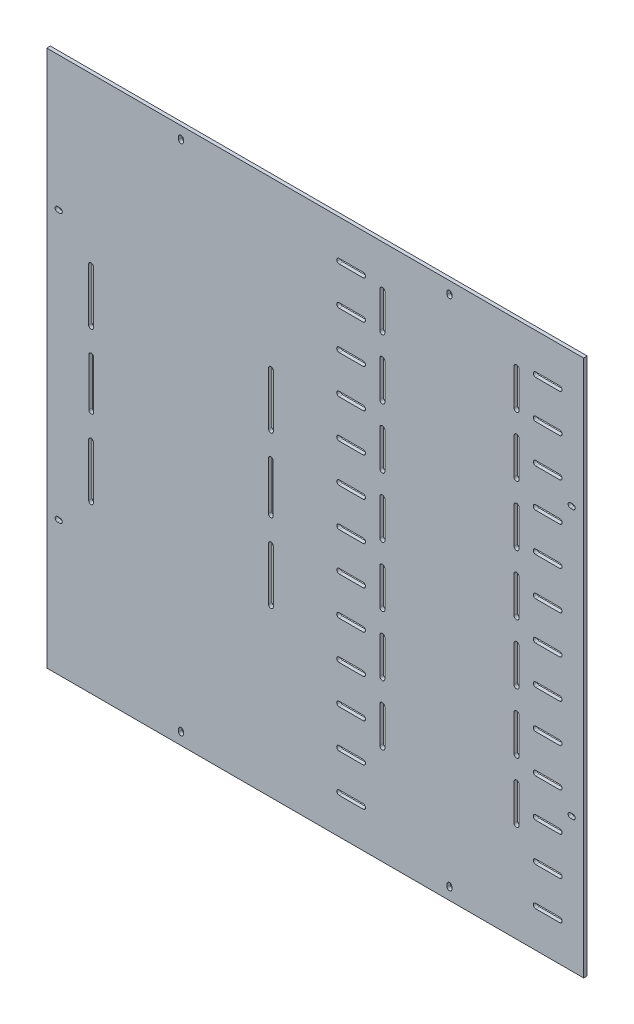
SolidWorks part; units mm, degrees
ref_plane "Piano frontale" through (0, 0, 0) normal (0, 0, 1) x (1, 0, 0)
ref_plane "Piano superiore" through (0, 0, 0) normal (0, 1, 0) x (1, 0, 0)
ref_plane "Piano destro" through (0, 0, 0) normal (1, 0, 0) x (0, 0, -1)
sketch "Schizzo1" plane through (0, 0, 0) normal (0, 0, 1) x (1, 0, 0)
  line L0 (10, 448) -> (10, -28.2593) construction
  line L1 (0, 0) -> (448, 0)
  line L2 (0, 0) -> (0, 448)
  line L3 (0, 448) -> (448, 448)
  line L4 (448, 0) -> (448, 448)
  line L5 (0, 224) -> (448, 224) construction
  line L6 (224, 448) -> (224, 0) construction
  line L7 (438, 448) -> (438, -28.2593) construction
  line L8 (0, 438) -> (525.0128, 438) construction
  line L9 (0, 10) -> (525.0128, 10) construction
  line L10 (0, 448) -> (0, 224) construction
  line L11 (0, 448) -> (0, 224) construction
  line L12 (9, 336) -> (11, 336) construction
  line L13 (9, 338) -> (11, 338)
  line L14 (9, 334) -> (11, 334)
  line L15 (0, 336) -> (224, 336) construction
  line L16 (9, 112) -> (11, 112) construction
  line L17 (9, 110) -> (11, 110)
  line L18 (9, 114) -> (11, 114)
  line L19 (439, 112) -> (437, 112) construction
  line L20 (439, 110) -> (437, 110)
  line L21 (439, 114) -> (437, 114)
  line L22 (439, 336) -> (437, 336) construction
  line L23 (439, 338) -> (437, 338)
  line L24 (439, 334) -> (437, 334)
  line L25 (112, 448) -> (112, 224) construction
  line L26 (112, 439) -> (112, 437) construction
  line L27 (114, 439) -> (114, 437)
  line L28 (110, 439) -> (110, 437)
  line L29 (336, 439) -> (336, 437) construction
  line L30 (334, 439) -> (334, 437)
  line L31 (338, 439) -> (338, 437)
  line L32 (112, 9) -> (112, 11) construction
  line L33 (114, 9) -> (114, 11)
  line L34 (110, 9) -> (110, 11)
  line L35 (336, 9) -> (336, 11) construction
  line L36 (334, 9) -> (334, 11)
  line L37 (338, 9) -> (338, 11)
  line L38 (36.9588, 287.1268) -> (36.9588, 448) construction
  line L39 (36.9588, 265.3661) -> (36.9588, 309.3661) construction
  line L40 (34.9588, 265.3661) -> (34.9588, 309.3661)
  line L41 (38.9588, 265.3661) -> (38.9588, 309.3661)
  line L42 (36.9588, 182.6339) -> (36.9588, 138.6339) construction
  line L43 (34.9588, 182.6339) -> (34.9588, 138.6339)
  line L44 (38.9588, 182.6339) -> (38.9588, 138.6339)
  line L45 (37.087, 204.1388) -> (37.087, 244.1388) construction
  line L46 (35.087, 204.1388) -> (35.087, 244.1388)
  line L47 (39.087, 204.1388) -> (39.087, 244.1388)
  line L48 (187.0412, 265.3661) -> (187.0412, 309.3661) construction
  line L49 (189.0412, 265.3661) -> (189.0412, 309.3661)
  line L50 (185.0412, 265.3661) -> (185.0412, 309.3661)
  line L51 (186.913, 204.1388) -> (186.913, 244.1388) construction
  line L52 (188.913, 204.1388) -> (188.913, 244.1388)
  line L53 (184.913, 204.1388) -> (184.913, 244.1388)
  line L54 (187.0412, 182.6339) -> (187.0412, 138.6339) construction
  line L55 (189.0412, 182.6339) -> (189.0412, 138.6339)
  line L56 (185.0412, 182.6339) -> (185.0412, 138.6339)
  line L57 (243.9707, 416) -> (263.9707, 416) construction
  line L58 (243.9707, 418) -> (263.9707, 418)
  line L59 (243.9707, 414) -> (263.9707, 414)
  line L63 (224, 224) -> (448, 0) construction
  line L64 (448, 224) -> (224, 0) construction
  line L65 (224, 224) -> (448, 224) construction
  line L66 (336, 112) -> (335.9892, 224.0001) construction
  line L67 (336, 112) -> (448, 112) construction
  line L83 (427.9707, 416.0177) -> (407.9707, 416.0139) construction
  line L84 (427.9703, 418.0177) -> (407.9703, 418.0139)
  line L85 (427.9711, 414.0177) -> (407.9711, 414.0139)
  line L89 (243.9707, 384) -> (263.9707, 384) construction
  line L90 (243.9707, 386) -> (263.9707, 386)
  line L91 (243.9707, 382) -> (263.9707, 382)
  line L92 (427.9707, 384.0177) -> (407.9707, 384.0139) construction
  line L93 (427.9703, 386.0177) -> (407.9703, 386.0139)
  line L94 (427.9711, 382.0177) -> (407.9711, 382.0139)
  line L95 (279.9725, 383.005) -> (279.9725, 412.995) construction
  line L96 (277.8725, 383.005) -> (277.8725, 412.995)
  line L97 (282.0725, 383.005) -> (282.0725, 412.995)
  line L98 (243.9707, 352) -> (263.9707, 352) construction
  line L99 (243.9707, 354) -> (263.9707, 354)
  line L100 (243.9707, 350) -> (263.9707, 350)
  line L101 (427.9707, 352.0177) -> (407.9707, 352.0139) construction
  line L102 (427.9703, 354.0177) -> (407.9703, 354.0139)
  line L103 (427.9711, 350.0177) -> (407.9711, 350.0139)
  line L104 (243.9707, 320) -> (263.9707, 320) construction
  line L105 (243.9707, 322) -> (263.9707, 322)
  line L106 (243.9707, 318) -> (263.9707, 318)
  line L107 (427.9707, 320.0177) -> (407.9707, 320.0139) construction
  line L108 (427.9703, 322.0177) -> (407.9703, 322.0139)
  line L109 (427.9711, 318.0177) -> (407.9711, 318.0139)
  line L110 (243.9707, 288) -> (263.9707, 288) construction
  line L111 (391.9724, 383.0058) -> (391.9724, 413.0158) construction
  line L112 (394.0724, 383.0058) -> (394.0724, 413.0158)
  line L113 (389.8724, 383.0058) -> (389.8724, 413.0158)
  line L114 (336, 112) -> (202.345, 112) construction
  line L118 (243.9707, 290) -> (263.9707, 290)
  line L122 (243.9707, 286) -> (263.9707, 286)
  line L132 (427.9707, 288.0177) -> (407.9707, 288.0139) construction
  line L133 (427.9703, 290.0177) -> (407.9703, 290.0139)
  line L134 (427.9711, 286.0177) -> (407.9711, 286.0139)
  line L135 (243.9707, 256) -> (263.9707, 256) construction
  line L136 (243.9707, 258) -> (263.9707, 258)
  line L137 (243.9707, 254) -> (263.9707, 254)
  line L138 (427.9707, 256.0177) -> (407.9707, 256.0139) construction
  line L139 (427.9703, 258.0177) -> (407.9703, 258.0139)
  line L140 (427.9711, 254.0177) -> (407.9711, 254.0139)
  line L141 (243.9707, 224) -> (263.9707, 224) construction
  line L142 (243.9707, 226) -> (263.9707, 226)
  line L143 (243.9707, 222) -> (263.9707, 222)
  line L144 (427.9707, 224.0177) -> (407.9707, 224.0139) construction
  line L145 (427.9703, 226.0177) -> (407.9703, 226.0139)
  line L146 (427.9711, 222.0177) -> (407.9711, 222.0139)
  line L147 (243.9707, 192) -> (263.9707, 192) construction
  line L148 (243.9707, 194) -> (263.9707, 194)
  line L149 (243.9707, 190) -> (263.9707, 190)
  line L150 (427.9707, 192.0177) -> (407.9707, 192.0139) construction
  line L151 (427.9703, 194.0177) -> (407.9703, 194.0139)
  line L152 (427.9711, 190.0177) -> (407.9711, 190.0139)
  line L153 (243.9707, 160) -> (263.9707, 160) construction
  line L154 (243.9707, 162) -> (263.9707, 162)
  line L155 (243.9707, 158) -> (263.9707, 158)
  line L156 (427.9707, 160.0177) -> (407.9707, 160.0139) construction
  line L157 (427.9703, 162.0177) -> (407.9703, 162.0139)
  line L158 (427.9711, 158.0177) -> (407.9711, 158.0139)
  line L159 (243.9707, 128) -> (263.9707, 128) construction
  line L160 (243.9707, 130) -> (263.9707, 130)
  line L161 (243.9707, 126) -> (263.9707, 126)
  line L162 (427.9707, 128.0177) -> (407.9707, 128.0139) construction
  line L163 (427.9703, 130.0177) -> (407.9703, 130.0139)
  line L164 (427.9711, 126.0177) -> (407.9711, 126.0139)
  line L165 (279.9725, 333.005) -> (279.9725, 362.995) construction
  line L166 (277.8725, 333.005) -> (277.8725, 362.995)
  line L167 (282.0725, 333.005) -> (282.0725, 362.995)
  line L168 (391.9724, 333.0058) -> (391.9724, 363.0158) construction
  line L169 (394.0724, 333.0058) -> (394.0724, 363.0158)
  line L170 (389.8724, 333.0058) -> (389.8724, 363.0158)
  line L171 (279.9725, 283.005) -> (279.9725, 312.995) construction
  line L172 (277.8725, 283.005) -> (277.8725, 312.995)
  line L173 (282.0725, 283.005) -> (282.0725, 312.995)
  line L174 (391.9724, 283.0058) -> (391.9724, 313.0158) construction
  line L175 (394.0724, 283.0058) -> (394.0724, 313.0158)
  line L176 (389.8724, 283.0058) -> (389.8724, 313.0158)
  line L177 (279.9725, 233.005) -> (279.9725, 262.995) construction
  line L178 (277.8725, 233.005) -> (277.8725, 262.995)
  line L179 (282.0725, 233.005) -> (282.0725, 262.995)
  line L180 (391.9724, 233.0058) -> (391.9724, 263.0158) construction
  line L181 (394.0724, 233.0058) -> (394.0724, 263.0158)
  line L182 (389.8724, 233.0058) -> (389.8724, 263.0158)
  line L183 (279.9725, 183.005) -> (279.9725, 212.995) construction
  line L184 (277.8725, 183.005) -> (277.8725, 212.995)
  line L185 (282.0725, 183.005) -> (282.0725, 212.995)
  line L186 (391.9724, 183.0058) -> (391.9724, 213.0158) construction
  line L187 (394.0724, 183.0058) -> (394.0724, 213.0158)
  line L188 (389.8724, 183.0058) -> (389.8724, 213.0158)
  line L189 (279.9725, 133.005) -> (279.9725, 162.995) construction
  line L190 (277.8725, 133.005) -> (277.8725, 162.995)
  line L191 (282.0725, 133.005) -> (282.0725, 162.995)
  line L192 (391.9724, 133.0058) -> (391.9724, 163.0158) construction
  line L193 (394.0724, 133.0058) -> (394.0724, 163.0158)
  line L194 (389.8724, 133.0058) -> (389.8724, 163.0158)
  line L195 (279.9725, 83.005) -> (279.9725, 112.995) construction
  line L196 (277.8725, 83.005) -> (277.8725, 112.995)
  line L197 (282.0725, 83.005) -> (282.0725, 112.995)
  line L198 (391.9724, 83.0058) -> (391.9724, 113.0158) construction
  line L199 (394.0724, 83.0058) -> (394.0724, 113.0158)
  line L200 (389.8724, 83.0058) -> (389.8724, 113.0158)
  line L201 (243.9707, 96) -> (263.9707, 96) construction
  line L202 (243.9707, 98) -> (263.9707, 98)
  line L203 (243.9707, 94) -> (263.9707, 94)
  line L204 (427.9707, 96.0177) -> (407.9707, 96.0139) construction
  line L205 (427.9703, 98.0177) -> (407.9703, 98.0139)
  line L206 (427.9711, 94.0177) -> (407.9711, 94.0139)
  line L207 (243.9707, 64) -> (263.9707, 64) construction
  line L208 (243.9707, 66) -> (263.9707, 66)
  line L209 (243.9707, 62) -> (263.9707, 62)
  line L210 (427.9707, 64.0177) -> (407.9707, 64.0139) construction
  line L211 (427.9703, 66.0177) -> (407.9703, 66.0139)
  line L212 (427.9711, 62.0177) -> (407.9711, 62.0139)
  line L213 (243.9707, 32) -> (263.9707, 32) construction
  line L214 (243.9707, 34) -> (263.9707, 34)
  line L215 (243.9707, 30) -> (263.9707, 30)
  line L216 (427.9707, 32.0177) -> (407.9707, 32.0139) construction
  line L217 (427.9703, 34.0177) -> (407.9703, 34.0139)
  line L218 (427.9711, 30.0177) -> (407.9711, 30.0139)
  arc A0 (9, 338) -> (9, 334) centre (9, 336) ccw
  arc A1 (11, 334) -> (11, 338) centre (11, 336) ccw
  arc A2 (9, 110) -> (9, 114) centre (9, 112) cw
  arc A3 (11, 114) -> (11, 110) centre (11, 112) cw
  arc A4 (439, 110) -> (439, 114) centre (439, 112) ccw
  arc A5 (437, 114) -> (437, 110) centre (437, 112) ccw
  arc A6 (439, 338) -> (439, 334) centre (439, 336) cw
  arc A7 (437, 334) -> (437, 338) centre (437, 336) cw
  arc A8 (114, 439) -> (110, 439) centre (112, 439) ccw
  arc A9 (110, 437) -> (114, 437) centre (112, 437) ccw
  arc A10 (334, 439) -> (338, 439) centre (336, 439) cw
  arc A11 (338, 437) -> (334, 437) centre (336, 437) cw
  arc A12 (114, 9) -> (110, 9) centre (112, 9) cw
  arc A13 (110, 11) -> (114, 11) centre (112, 11) cw
  arc A14 (334, 9) -> (338, 9) centre (336, 9) ccw
  arc A15 (338, 11) -> (334, 11) centre (336, 11) ccw
  arc A16 (34.9588, 265.3661) -> (38.9588, 265.3661) centre (36.9588, 265.3661) ccw
  arc A17 (38.9588, 309.3661) -> (34.9588, 309.3661) centre (36.9588, 309.3661) ccw
  arc A18 (34.9588, 182.6339) -> (38.9588, 182.6339) centre (36.9588, 182.6339) cw
  arc A19 (38.9588, 138.6339) -> (34.9588, 138.6339) centre (36.9588, 138.6339) cw
  arc A20 (35.087, 204.1388) -> (39.087, 204.1388) centre (37.087, 204.1388) ccw
  arc A21 (39.087, 244.1388) -> (35.087, 244.1388) centre (37.087, 244.1388) ccw
  arc A22 (189.0412, 265.3661) -> (185.0412, 265.3661) centre (187.0412, 265.3661) cw
  arc A23 (185.0412, 309.3661) -> (189.0412, 309.3661) centre (187.0412, 309.3661) cw
  arc A24 (188.913, 204.1388) -> (184.913, 204.1388) centre (186.913, 204.1388) cw
  arc A25 (184.913, 244.1388) -> (188.913, 244.1388) centre (186.913, 244.1388) cw
  arc A26 (189.0412, 182.6339) -> (185.0412, 182.6339) centre (187.0412, 182.6339) ccw
  arc A27 (185.0412, 138.6339) -> (189.0412, 138.6339) centre (187.0412, 138.6339) ccw
  arc A28 (243.9707, 418) -> (243.9707, 414) centre (243.9707, 416) ccw
  arc A29 (263.9707, 414) -> (263.9707, 418) centre (263.9707, 416) ccw
  arc A36 (427.9703, 418.0177) -> (427.9711, 414.0177) centre (427.9707, 416.0177) cw
  arc A37 (407.9711, 414.0139) -> (407.9703, 418.0139) centre (407.9707, 416.0139) cw
  arc A38 (243.9707, 386) -> (243.9707, 382) centre (243.9707, 384) ccw
  arc A39 (263.9707, 382) -> (263.9707, 386) centre (263.9707, 384) ccw
  arc A40 (427.9703, 386.0177) -> (427.9711, 382.0177) centre (427.9707, 384.0177) cw
  arc A41 (407.9711, 382.0139) -> (407.9703, 386.0139) centre (407.9707, 384.0139) cw
  arc A42 (243.9707, 354) -> (243.9707, 350) centre (243.9707, 352) ccw
  arc A43 (263.9707, 350) -> (263.9707, 354) centre (263.9707, 352) ccw
  arc A44 (427.9703, 354.0177) -> (427.9711, 350.0177) centre (427.9707, 352.0177) cw
  arc A45 (407.9711, 350.0139) -> (407.9703, 354.0139) centre (407.9707, 352.0139) cw
  arc A52 (243.9707, 322) -> (243.9707, 318) centre (243.9707, 320) ccw
  arc A53 (263.9707, 318) -> (263.9707, 322) centre (263.9707, 320) ccw
  arc A56 (427.9703, 322.0177) -> (427.9711, 318.0177) centre (427.9707, 320.0177) cw
  arc A57 (407.9711, 318.0139) -> (407.9703, 322.0139) centre (407.9707, 320.0139) cw
  arc A58 (243.9707, 290) -> (243.9707, 286) centre (243.9707, 288) ccw
  arc A59 (263.9707, 286) -> (263.9707, 290) centre (263.9707, 288) ccw
  arc A60 (277.8725, 383.005) -> (282.0725, 383.005) centre (279.9725, 383.005) ccw
  arc A61 (282.0725, 412.995) -> (277.8725, 412.995) centre (279.9725, 412.995) ccw
  arc A62 (427.9703, 290.0177) -> (427.9711, 286.0177) centre (427.9707, 288.0177) cw
  arc A63 (407.9711, 286.0139) -> (407.9703, 290.0139) centre (407.9707, 288.0139) cw
  arc A64 (243.9707, 258) -> (243.9707, 254) centre (243.9707, 256) ccw
  arc A65 (263.9707, 254) -> (263.9707, 258) centre (263.9707, 256) ccw
  arc A66 (427.9703, 258.0177) -> (427.9711, 254.0177) centre (427.9707, 256.0177) cw
  arc A67 (407.9711, 254.0139) -> (407.9703, 258.0139) centre (407.9707, 256.0139) cw
  arc A68 (243.9707, 226) -> (243.9707, 222) centre (243.9707, 224) ccw
  arc A69 (263.9707, 222) -> (263.9707, 226) centre (263.9707, 224) ccw
  arc A70 (394.0724, 383.0058) -> (389.8724, 383.0058) centre (391.9724, 383.0058) cw
  arc A71 (389.8724, 413.0158) -> (394.0724, 413.0158) centre (391.9724, 413.0158) cw
  arc A82 (427.9703, 226.0177) -> (427.9711, 222.0177) centre (427.9707, 224.0177) cw
  arc A83 (407.9711, 222.0139) -> (407.9703, 226.0139) centre (407.9707, 224.0139) cw
  arc A84 (243.9707, 194) -> (243.9707, 190) centre (243.9707, 192) ccw
  arc A85 (263.9707, 190) -> (263.9707, 194) centre (263.9707, 192) ccw
  arc A86 (427.9703, 194.0177) -> (427.9711, 190.0177) centre (427.9707, 192.0177) cw
  arc A87 (407.9711, 190.0139) -> (407.9703, 194.0139) centre (407.9707, 192.0139) cw
  arc A88 (243.9707, 162) -> (243.9707, 158) centre (243.9707, 160) ccw
  arc A89 (263.9707, 158) -> (263.9707, 162) centre (263.9707, 160) ccw
  arc A90 (427.9703, 162.0177) -> (427.9711, 158.0177) centre (427.9707, 160.0177) cw
  arc A91 (407.9711, 158.0139) -> (407.9703, 162.0139) centre (407.9707, 160.0139) cw
  arc A92 (243.9707, 130) -> (243.9707, 126) centre (243.9707, 128) ccw
  arc A93 (263.9707, 126) -> (263.9707, 130) centre (263.9707, 128) ccw
  arc A94 (427.9703, 130.0177) -> (427.9711, 126.0177) centre (427.9707, 128.0177) cw
  arc A95 (407.9711, 126.0139) -> (407.9703, 130.0139) centre (407.9707, 128.0139) cw
  arc A96 (277.8725, 333.005) -> (282.0725, 333.005) centre (279.9725, 333.005) ccw
  arc A97 (282.0725, 362.995) -> (277.8725, 362.995) centre (279.9725, 362.995) ccw
  arc A98 (394.0724, 333.0058) -> (389.8724, 333.0058) centre (391.9724, 333.0058) cw
  arc A99 (389.8724, 363.0158) -> (394.0724, 363.0158) centre (391.9724, 363.0158) cw
  arc A100 (277.8725, 283.005) -> (282.0725, 283.005) centre (279.9725, 283.005) ccw
  arc A101 (282.0725, 312.995) -> (277.8725, 312.995) centre (279.9725, 312.995) ccw
  arc A102 (394.0724, 283.0058) -> (389.8724, 283.0058) centre (391.9724, 283.0058) cw
  arc A103 (389.8724, 313.0158) -> (394.0724, 313.0158) centre (391.9724, 313.0158) cw
  arc A104 (277.8725, 233.005) -> (282.0725, 233.005) centre (279.9725, 233.005) ccw
  arc A105 (282.0725, 262.995) -> (277.8725, 262.995) centre (279.9725, 262.995) ccw
  arc A106 (394.0724, 233.0058) -> (389.8724, 233.0058) centre (391.9724, 233.0058) cw
  arc A107 (389.8724, 263.0158) -> (394.0724, 263.0158) centre (391.9724, 263.0158) cw
  arc A108 (277.8725, 183.005) -> (282.0725, 183.005) centre (279.9725, 183.005) ccw
  arc A109 (282.0725, 212.995) -> (277.8725, 212.995) centre (279.9725, 212.995) ccw
  arc A110 (394.0724, 183.0058) -> (389.8724, 183.0058) centre (391.9724, 183.0058) cw
  arc A111 (389.8724, 213.0158) -> (394.0724, 213.0158) centre (391.9724, 213.0158) cw
  arc A112 (277.8725, 133.005) -> (282.0725, 133.005) centre (279.9725, 133.005) ccw
  arc A113 (282.0725, 162.995) -> (277.8725, 162.995) centre (279.9725, 162.995) ccw
  arc A114 (394.0724, 133.0058) -> (389.8724, 133.0058) centre (391.9724, 133.0058) cw
  arc A115 (389.8724, 163.0158) -> (394.0724, 163.0158) centre (391.9724, 163.0158) cw
  arc A116 (277.8725, 83.005) -> (282.0725, 83.005) centre (279.9725, 83.005) ccw
  arc A117 (282.0725, 112.995) -> (277.8725, 112.995) centre (279.9725, 112.995) ccw
  arc A118 (394.0724, 83.0058) -> (389.8724, 83.0058) centre (391.9724, 83.0058) cw
  arc A119 (389.8724, 113.0158) -> (394.0724, 113.0158) centre (391.9724, 113.0158) cw
  arc A120 (243.9707, 98) -> (243.9707, 94) centre (243.9707, 96) ccw
  arc A121 (263.9707, 94) -> (263.9707, 98) centre (263.9707, 96) ccw
  arc A122 (427.9703, 98.0177) -> (427.9711, 94.0177) centre (427.9707, 96.0177) cw
  arc A123 (407.9711, 94.0139) -> (407.9703, 98.0139) centre (407.9707, 96.0139) cw
  arc A124 (243.9707, 66) -> (243.9707, 62) centre (243.9707, 64) ccw
  arc A125 (263.9707, 62) -> (263.9707, 66) centre (263.9707, 64) ccw
  arc A126 (427.9703, 66.0177) -> (427.9711, 62.0177) centre (427.9707, 64.0177) cw
  arc A127 (407.9711, 62.0139) -> (407.9703, 66.0139) centre (407.9707, 64.0139) cw
  arc A128 (243.9707, 34) -> (243.9707, 30) centre (243.9707, 32) ccw
  arc A129 (263.9707, 30) -> (263.9707, 34) centre (263.9707, 32) ccw
  arc A130 (427.9703, 34.0177) -> (427.9711, 30.0177) centre (427.9707, 32.0177) cw
  arc A131 (407.9711, 30.0139) -> (407.9703, 34.0139) centre (407.9707, 32.0139) cw
  point P19 (10, 336)
  point P28 (10, 112)
  point P35 (438, 112)
  point P42 (438, 336)
  point P49 (112, 438)
  point P52 (112, 438)
  point P59 (336, 438)
  point P66 (112, 10)
  point P73 (336, 10)
  point P82 (36.9588, 287.3661)
  point P89 (36.9588, 160.6339)
  point P96 (37.087, 224.1388)
  point P103 (187.0412, 287.3661)
  point P110 (186.913, 224.1388)
  point P117 (187.0412, 160.6339)
  point P124 (253.9707, 416)
  point P155 (417.9707, 416.0158)
  point P164 (253.9707, 384)
  point P171 (417.9707, 384.0158)
  point P179 (280.1758, 232.4048)
  point P193 (280.1085, 282.4047)
  point P197 (253.9707, 352)
  point P207 (280.0413, 332.4047)
  point P214 (417.9707, 352.0158)
  point P221 (253.9707, 320)
  point P227 (279.9725, 398)
  point P235 (417.9707, 320.0158)
  point P242 (253.9707, 288)
  point P249 (417.9707, 288.0158)
  point P256 (253.9707, 256)
  point P262 (391.9724, 398.0108)
  point P307 (417.9707, 256.0158)
  point P314 (253.9707, 224)
  point P321 (417.9707, 224.0158)
  point P328 (253.9707, 192)
  point P335 (417.9707, 192.0158)
  point P342 (253.9707, 160)
  point P349 (417.9707, 160.0158)
  point P356 (253.9707, 128)
  point P363 (417.9707, 128.0158)
  point P370 (279.9725, 348)
  point P377 (391.9724, 348.0108)
  point P384 (279.9725, 298)
  point P391 (391.9724, 298.0108)
  point P398 (279.9725, 248)
  point P405 (391.9724, 248.0108)
  point P412 (279.9725, 198)
  point P419 (391.9724, 198.0108)
  point P426 (279.9725, 148)
  point P433 (391.9724, 148.0108)
  point P440 (279.9725, 98)
  point P447 (391.9724, 98.0108)
  point P454 (253.9707, 96)
  point P461 (417.9707, 96.0158)
  point P468 (253.9707, 64)
  point P475 (417.9707, 64.0158)
  point P482 (253.9707, 32)
  point P489 (417.9707, 32.0158)
  dimension "D5" = 1
  dimension "D14" = 82
  dimension "D21" = 7
  dimension "D1" = 448
  dimension "D2" = 448
  dimension "D3" = 10
  dimension "D4" = 10
  dimension "D6" = 4
  dimension "D7" = 112
  dimension "D8" = 112
  dimension "D9" = 1
  dimension "D10" = 4
  dimension "D11" = 4
  dimension "D12" = 22
  dimension "D13" = 4
  dimension "D15" = 32
  dimension "D16" = 20
  dimension "D17" = 50
  dimension "D25" = 112
extrude "Estrusione-Estrusione1" add sketch "Schizzo1" against normal blind 3
